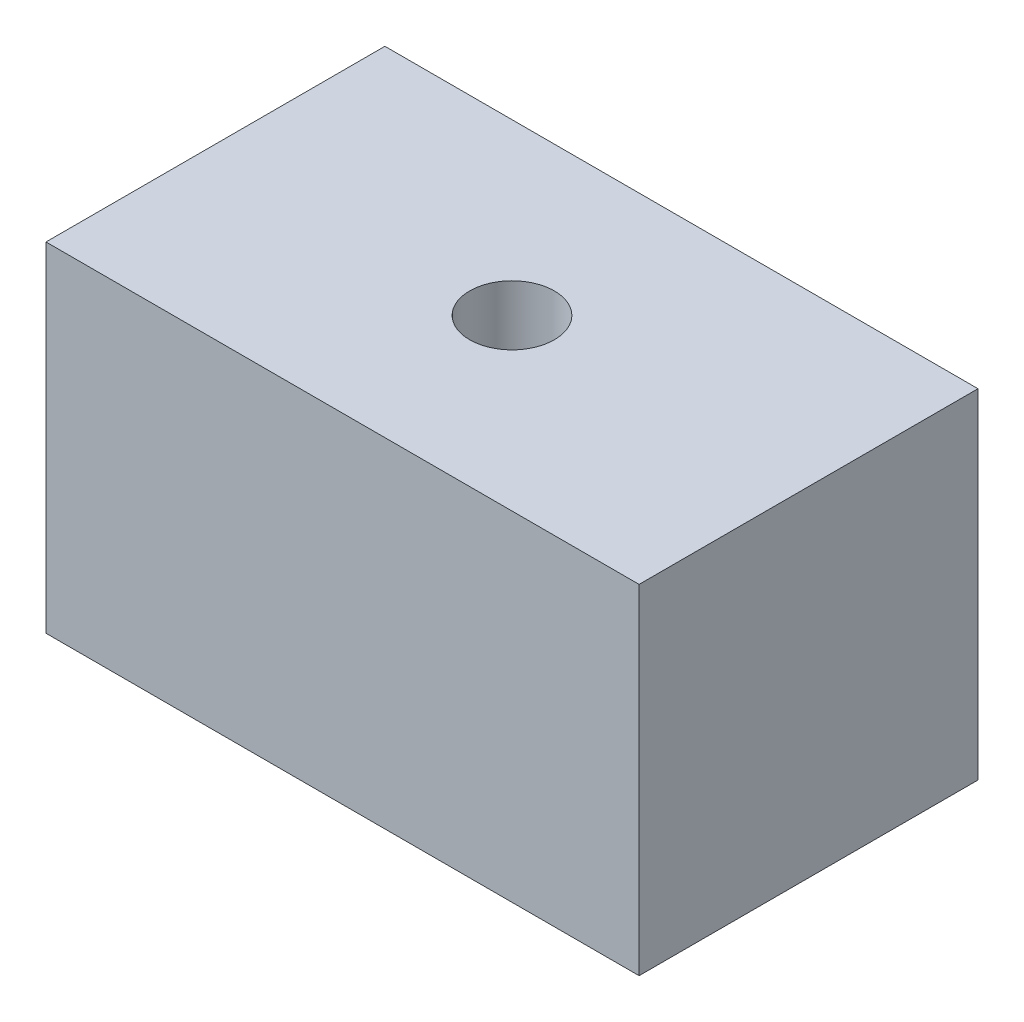
SolidWorks part; units mm, degrees
ref_plane "Front Plane" through (0, 0, 0) normal (0, 0, 1) x (1, 0, 0)
ref_plane "Top Plane" through (0, 0, 0) normal (0, 1, 0) x (1, 0, 0)
ref_plane "Right Plane" through (0, 0, 0) normal (1, 0, 0) x (0, 0, -1)
sketch "Sketch1" plane through (0, 0, 0) normal (0, 1, 0) x (1, 0, 0)
  line L1 (-44.45, -25.4) -> (44.45, -25.4)
  line L2 (-44.45, -25.4) -> (-44.45, 25.4)
  line L3 (-44.45, 25.4) -> (44.45, 25.4)
  line L4 (44.45, -25.4) -> (44.45, 25.4)
  line L5 (-44.45, -25.4) -> (44.45, 25.4) construction
  line L6 (-44.45, 25.4) -> (44.45, -25.4) construction
  circle A0 centre (0, 0) radius 6.35
  point P0 (0, 0)
  dimension "D3" = 12.7
  dimension "D1" = 88.9
  dimension "D2" = 50.8
extrude "Boss-Extrude2" add sketch "Sketch1" along normal blind 50.8
